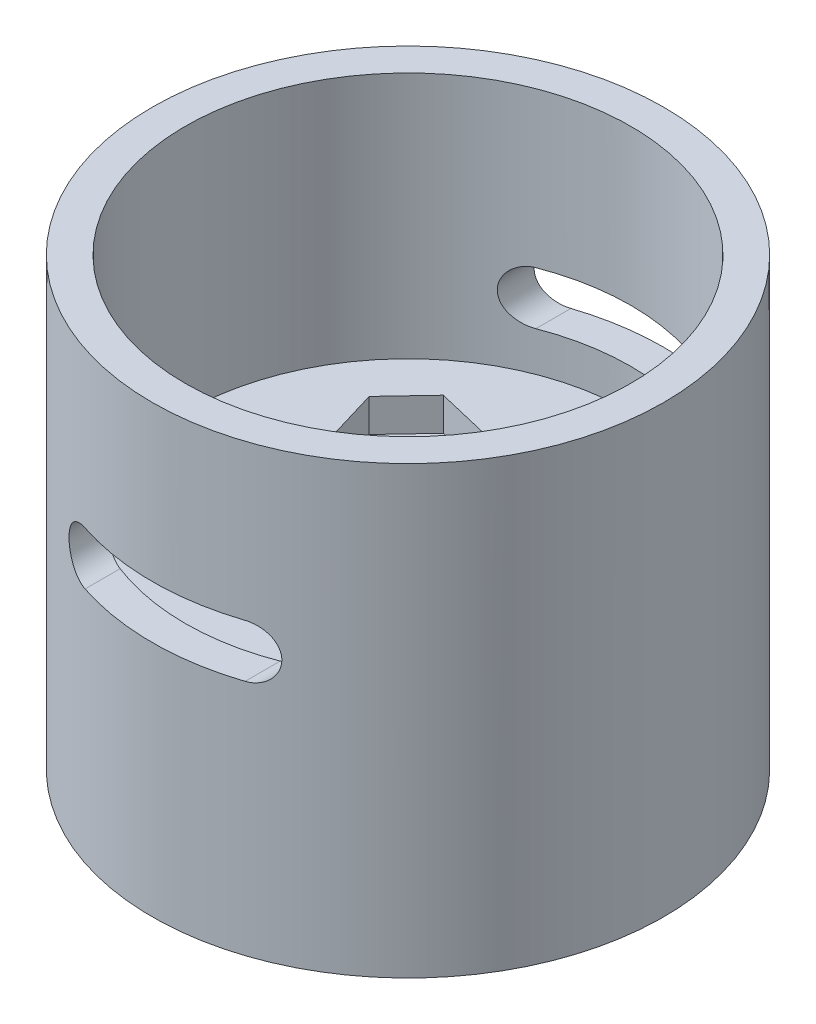
SolidWorks part; units mm, degrees
ref_plane "Front Plane" through (0, 0, 0) normal (0, 0, 1) x (1, 0, 0)
ref_plane "Top Plane" through (0, 0, 0) normal (0, 1, 0) x (1, 0, 0)
ref_plane "Right Plane" through (0, 0, 0) normal (1, 0, 0) x (0, 0, -1)
sketch "Sketch1" plane through (0, 0, 0) normal (0, 1, 0) x (1, 0, 0)
  circle A0 centre (0, 0) radius 13.5
  circle A1 centre (0, 0) radius 15.5
  dimension "D1" = 27
  dimension "D2" = 2
extrude "Boss-Extrude1" add sketch "Sketch1" along normal blind 18
extrude "Boss-Extrude2" add sketch "Sketch1<3>" along normal blind 3 contours A0
sketch "Sketch1<3>" plane through (0, 0, 0) normal (0, 1, 0) x (1, 0, 0) same geometry as "Sketch1"
sketch "Sketch2" plane through (0, 3, 0) normal (0, 1, 0) x (1, 0, 0)
  circle A0 centre (0, 0) radius 5.2
  circle A1 centre (-5.6543, 5.6595) radius 1.65
  circle A2 centre (0, 0) radius 5.2
  circle A3 centre (5.6595, 5.6543) radius 1.65
  circle A4 centre (0, 0) radius 5.2
  circle A5 centre (5.6543, -5.6595) radius 1.65
  circle A6 centre (0, 0) radius 5.2
  circle A7 centre (-5.6595, -5.6543) radius 1.65
  point P17 (0, 0)
  dimension "D1" = 10.4
  dimension "D3" = 3.3
  dimension "D2" = 8
  dimension "D4" = 4
extrude "Cut-Extrude4" cut sketch "Sketch2" against normal blind 41 contours A1 | A5 | A3 | A0 | A7 region at (0, 3, 0) region at (-5.6543, 3, -5.6595) region at (5.6595, 3, -5.6543) region at (5.6543, 3, 5.6595) region at (-5.6595, 3, 5.6543)
sketch "Sketch3" plane through (0, 3, 0) normal (0, 1, 0) x (1, 0, 0)
  line L7 (-7.8344, 3.3507) -> (-4.7449, 2.617)
  line L8 (-4.7449, 2.617) -> (-2.5648, 4.9257)
  line L9 (-2.5648, 4.9257) -> (-3.4741, 7.9682)
  line L10 (-3.4741, 7.9682) -> (-6.5636, 8.7019)
  line L11 (-6.5636, 8.7019) -> (-8.7437, 6.3932)
  line L12 (-8.7437, 6.3932) -> (-7.8344, 3.3507)
  line L13 (3.3507, 7.8344) -> (2.617, 4.7449)
  line L14 (2.617, 4.7449) -> (4.9257, 2.5648)
  line L15 (4.9257, 2.5648) -> (7.9682, 3.4741)
  line L16 (7.9682, 3.4741) -> (8.7019, 6.5636)
  line L17 (8.7019, 6.5636) -> (6.3932, 8.7437)
  line L18 (6.3932, 8.7437) -> (3.3507, 7.8344)
  line L19 (7.8344, -3.3507) -> (4.7449, -2.617)
  line L20 (4.7449, -2.617) -> (2.5648, -4.9257)
  line L21 (2.5648, -4.9257) -> (3.4741, -7.9682)
  line L22 (3.4741, -7.9682) -> (6.5636, -8.7019)
  line L23 (6.5636, -8.7019) -> (8.7437, -6.3932)
  line L24 (8.7437, -6.3932) -> (7.8344, -3.3507)
  line L25 (-3.3507, -7.8344) -> (-2.617, -4.7449)
  line L26 (-2.617, -4.7449) -> (-4.9257, -2.5648)
  line L27 (-4.9257, -2.5648) -> (-7.9682, -3.4741)
  line L28 (-7.9682, -3.4741) -> (-8.7019, -6.5636)
  line L29 (-8.7019, -6.5636) -> (-6.3932, -8.7437)
  line L30 (-6.3932, -8.7437) -> (-3.3507, -7.8344)
  circle A0 centre (-5.6543, 5.6595) radius 2.75 construction
  point P30 (0, 0)
  point P31 (-7.423, 9.6086)
  dimension "D1" = 5.5
  dimension "D2" = 4
extrude "Cut-Extrude5" cut sketch "Sketch3" against normal blind 2
sketch "Sketch4" plane through (0, 0, 0) normal (0, 0, 1) x (1, 0, 0)
  line L0 (4.8489, 7) -> (-4.8489, 7) construction
  line L1 (4.8489, 5.4) -> (-4.8489, 5.4)
  line L2 (4.8489, 8.6) -> (-4.8489, 8.6)
  line L3 (13.5, 3) -> (-13.5, 3) construction
  arc A0 (4.8489, 5.4) -> (4.8489, 8.6) centre (4.8489, 7) ccw
  arc A1 (-4.8489, 8.6) -> (-4.8489, 5.4) centre (-4.8489, 7) ccw
  point P2 (0, 7)
  dimension "D2" = 1.6
  dimension "D1" = 4
extrude "Cut-Extrude6" cut sketch "Sketch4" against normal blind 16 and the other way blind 20
sketch "Sketch5" plane through (0, 0, 0) normal (0, -1, 0) x (1, 0, 0)
  circle A0 centre (0, 0) radius 15.5
  circle A1 centre (0, 0) radius 13.5
  dimension "D1" = 27
extrude "Boss-Extrude3" add sketch "Sketch5" along normal blind 9
